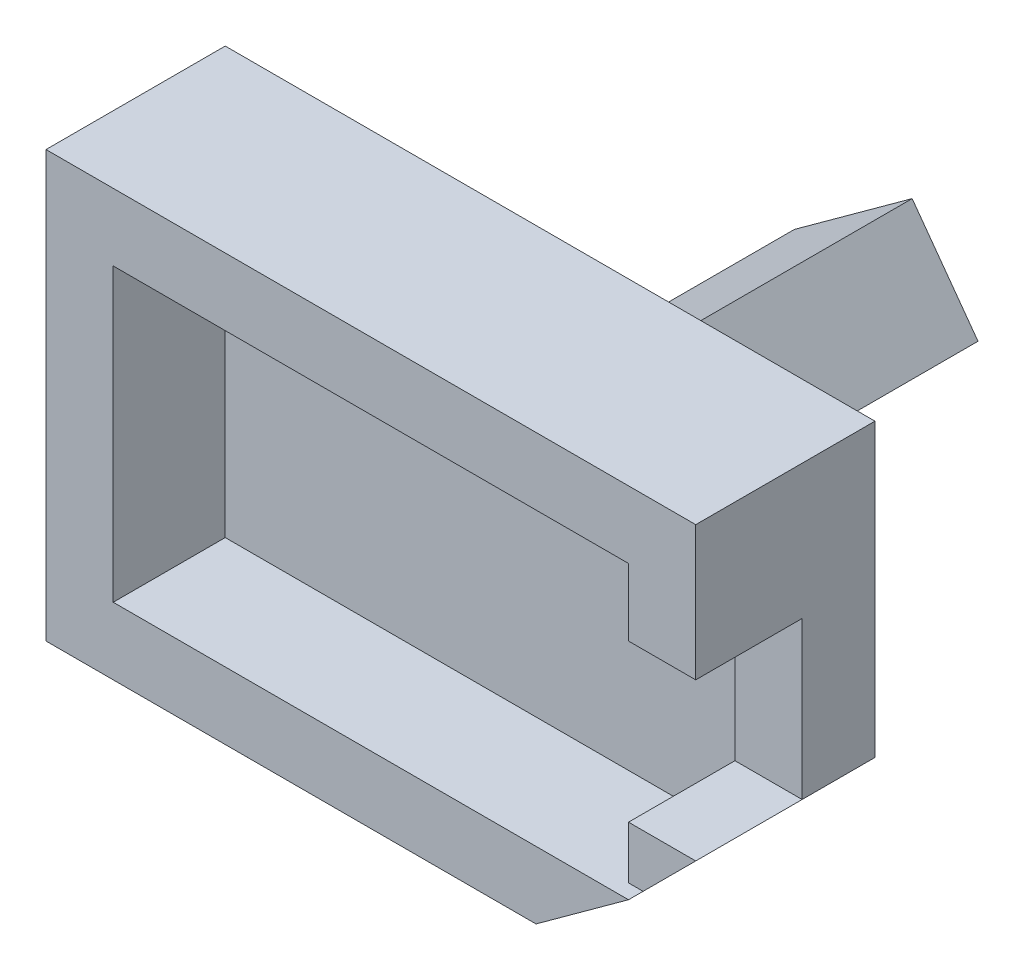
SolidWorks part; units mm, degrees
ref_plane "Front Plane" through (0, 0, 0) normal (0, 0, 1) x (1, 0, 0)
ref_plane "Top Plane" through (0, 0, 0) normal (0, 1, 0) x (1, 0, 0)
ref_plane "Right Plane" through (0, 0, 0) normal (1, 0, 0) x (0, 0, -1)
sketch "Sketch1" plane through (0, 0, 0) normal (0, 0, 1) x (1, 0, 0)
  line L0 (7.3709, -9.5) -> (-14.5, -9.5)
  line L1 (11.5, -6.5) -> (-11.5, -6.5) construction
  line L2 (11.5, -6.5) -> (11.5, 6.5) construction
  line L3 (11.5, 6.5) -> (-11.5, 6.5) construction
  line L4 (-11.5, -6.5) -> (-11.5, 6.5) construction
  line L5 (11.5, -6.5) -> (-11.5, 6.5) construction
  line L6 (11.5, 6.5) -> (-11.5, -6.5) construction
  line L7 (-14.5, -9.5) -> (-14.5, 9.5)
  line L8 (14.5, 9.5) -> (-14.5, 9.5)
  line L9 (14.5, -3.5) -> (14.5, 9.5)
  line L10 (14.5, -3.5) -> (11.5, -6.5)
  line L12 (7.3709, -9.5) -> (11.5, -6.5)
  line L13 (14.5, -9.5) -> (14.5, 9.5) construction
  line L14 (14.5, -9.5) -> (-14.5, -9.5) construction
  point P0 (0, 0)
  dimension "D1" = 13
  dimension "D2" = 23
  dimension "D4" = 45
  dimension "D5" = 36
  dimension "D3" = 3
extrude "Boss-Extrude1" add sketch "Sketch1" along normal blind 3
sketch "Sketch2" plane through (0, 0, 3) normal (0, 0, 1) x (1, 0, 0)
  line L0 (14.5, -3.5) -> (12.1512, -5.8488)
  line L1 (11.5, -6.5) -> (-11.5, -6.5)
  line L2 (11.5, -5.8488) -> (11.5, 6.5)
  line L3 (11.5, 6.5) -> (-11.5, 6.5)
  line L4 (-11.5, -6.5) -> (-11.5, 6.5)
  line L5 (11.5, -6.5) -> (-11.5, 6.5) construction
  line L6 (11.5, 6.5) -> (-11.5, -6.5) construction
  line L7 (7.3709, -9.5) -> (-14.5, -9.5)
  line L8 (14.5, -3.5) -> (14.5, 9.5)
  line L9 (14.5, 9.5) -> (-14.5, 9.5)
  line L10 (-14.5, -9.5) -> (-14.5, 9.5)
  line L11 (14.5, -9.5) -> (-14.5, 9.5) construction
  line L12 (14.5, 9.5) -> (-14.5, -9.5) construction
  line L13 (11.5, -5.8488) -> (12.1512, -5.8488)
  line L14 (11.5, -6.5) -> (7.3709, -9.5)
  point P0 (0, 0)
  point P7 (0, 0)
  dimension "D1" = 2.3488
  dimension "D2" = 45
  dimension "D3" = 13
  dimension "D4" = 5.1039
extrude "Boss-Extrude2" add sketch "Sketch2" along normal blind 5
sketch "Sketch3" plane through (0, 0, 0) normal (0, 0, -1) x (-1, 0, 0)
  line L0 (0, 0) -> (5.8546, 0) construction
  line L1 (-1.1598, 3.9328) -> (4.0988, 0.1122)
  line L2 (-1.1598, 3.9328) -> (-4.0988, -0.1122)
  line L3 (-4.0988, -0.1122) -> (1.1598, -3.9328)
  line L4 (4.0988, 0.1122) -> (1.1598, -3.9328)
  line L5 (-1.1598, 3.9328) -> (1.1598, -3.9328) construction
  line L6 (-4.0988, -0.1122) -> (4.0988, 0.1122) construction
  line L7 (0, 0) -> (4.1972, -3.0495) construction
  point P0 (0, 0)
  dimension "D1" = 36
  dimension "D2" = 5
  dimension "D3" = 5.188
  dimension "D4" = 6.5
extrude "Boss-Extrude3" add sketch "Sketch3" along normal blind 15
sketch "Sketch4" plane through (14.5, 0, 0) normal (1, 0, 0) x (0, 0, -1)
  line L0 (0, 0) -> (-4, 0) construction
  line L1 (-8, 3.5) -> (-8, -3.5)
  line L2 (-3.25, -3.5) -> (-8, -3.5)
  line L3 (-3.25, -3.5) -> (-3.25, 3.5)
  line L4 (-3.25, 3.5) -> (-8, 3.5)
  dimension "D1" = 4
  dimension "D2" = 0.75
  dimension "D3" = 7
  dimension "D4" = 4.75
extrude "Cut-Extrude1" cut sketch "Sketch4" against normal blind 8
